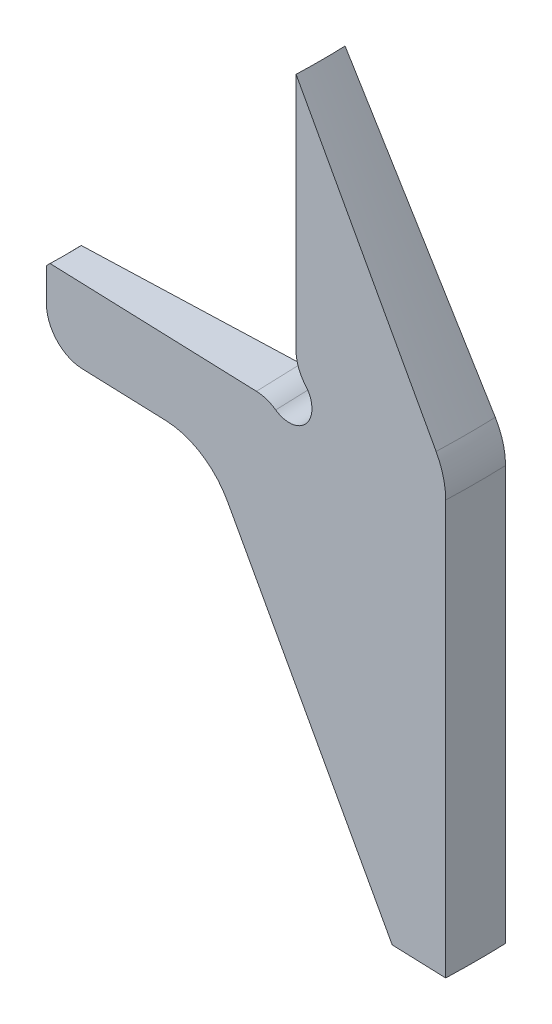
SolidWorks part; units mm, degrees
ref_plane "Front Plane" through (0, 0, 0) normal (0, 0, 1) x (1, 0, 0)
ref_plane "Top Plane" through (0, 0, 0) normal (0, 1, 0) x (1, 0, 0)
ref_plane "Right Plane" through (0, 0, 0) normal (1, 0, 0) x (0, 0, -1)
sketch "Sketch1" plane through (0, 0, 0) normal (0, 1, 0) x (1, 0, 0)
  line L0 (-190, 0) -> (0, 0) construction
  circle A0 centre (-190, 0) radius 190 construction
  dimension "D1" = 380
sketch "Sketch2" plane through (0, 0, 0) normal (0, 0, 1) x (1, 0, 0)
  line L0 (0, 80) -> (41.9615, 7.3205)
  line L1 (41.9615, 7.3205) -> (41.9615, -110)
  line L3 (-25, -20) -> (-70, -20)
  line L4 (-70, -20) -> (-70, 0)
  line L5 (0, 0) -> (-380, 0) construction
  line L6 (-70, 0) -> (0, 0)
  line L7 (0, 0) -> (0, 80)
  line L8 (41.9615, -110) -> (26.9615, -110)
  line L9 (26.9615, -110) -> (-25, -20)
  point P10 (-26.2397, -15)
  point P11 (-19.4478, -15)
  point P13 (53.7539, -105.8348)
  point P14 (-33.2202, -15)
  point P15 (24.3223, -80)
  point P16 (0, 104.7142)
  point P17 (43.9253, -80)
  point P18 (-22.5483, -15)
  point P19 (0, 112.7796)
  point P20 (43.8918, 3.9771)
  point P22 (0, 0)
  dimension "D1" = 20
  dimension "D2" = 15
  dimension "D3" = 110
  dimension "D4" = 80
  dimension "D5" = 190
  dimension "D6" = 70
  dimension "D7" = 120
  dimension "D8" = 45
ref_axis "Axis1" through (-190, 0, 0) along (0, 1, 0)
revolve "Revolve1" add sketch "Sketch2" angle 4 mid plane about axis through (-190, 0, 0) along (0, 1, 0) region at (8.4345, -22.9171, 0)
fillet "Fillet1" radius 20 2 edges at (-25, -20, 0) (41.9615, 7.3205, 0)
fillet "Fillet2" radius 10 1 edges at (-70, -20, 0)
chamfer "Chamfer1" distance 1 angle 45 1 edges at (-70, 0, 0)
sketch "Sketch3" plane through (-0.2314, 0, -6.6269) normal (-0.0349, 0, -0.9994) x (-0.9994, 0, 0.0349)
  circle A0 centre (2.489, 3.9753) radius 6.5881
  point P2 (2.0824, 3.2147)
  point P3 (5.894, 6.2918)
  point P4 (6.3681, 4.4775)
  point P5 (2.489, 3.9753)
extrude "Cut-Extrude1" cut sketch "Sketch3" against normal through all
fillet "Fillet3" radius 10 2 edges at (-7.747, 0, 0.0078)
